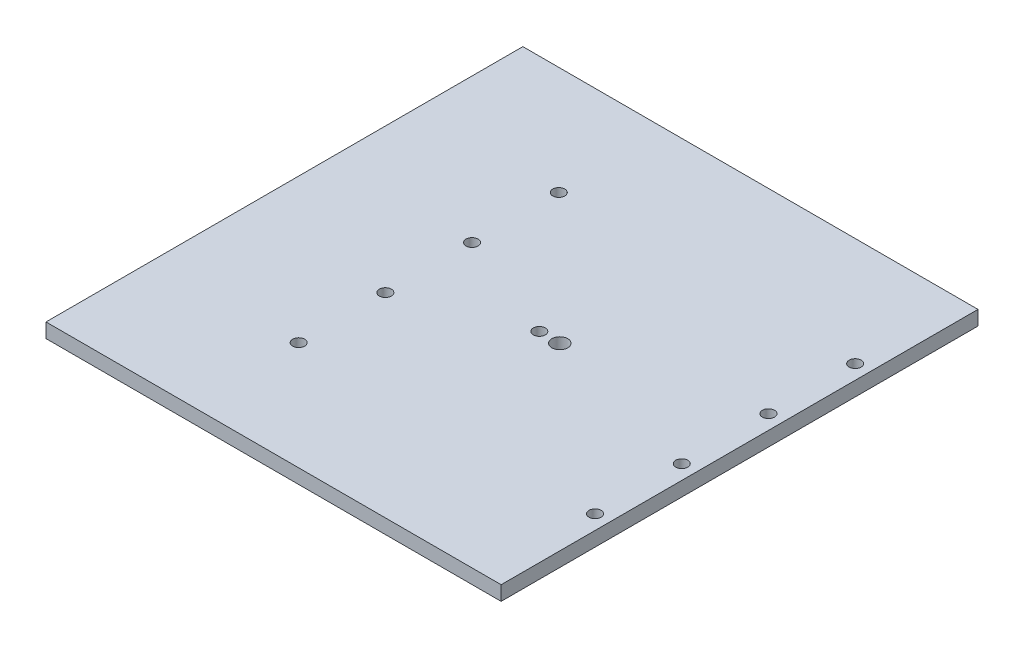
SolidWorks part; units mm, degrees
material "PE High Density"
ref_plane "Front Plane" through (0, 0, 0) normal (0, 0, 1) x (1, 0, 0)
ref_plane "Top Plane" through (0, 0, 0) normal (0, 1, 0) x (1, 0, 0)
ref_plane "Right Plane" through (0, 0, 0) normal (1, 0, 0) x (0, 0, -1)
sketch "Sketch1" plane through (0, 0, 0) normal (0, 1, 0) x (1, 0, 0)
  line L1 (-100, -104.775) -> (100, -104.775)
  line L2 (-100, -104.775) -> (-100, 104.775)
  line L3 (-100, 104.775) -> (100, 104.775)
  line L4 (100, -104.775) -> (100, 104.775)
  line L5 (-100, -104.775) -> (100, 104.775) construction
  line L6 (-100, 104.775) -> (100, -104.775) construction
  point P0 (0, 0)
  dimension "D1" = 200
  dimension "D2" = 209.55
extrude "Boss-Extrude1" add sketch "Sketch1" along normal mid plane 6.35
sketch "Sketch2" plane through (0, 3.175, 0) normal (0, 1, 0) x (1, 0, 0)
  line L0 (-100, -104.775) -> (100, -104.775) construction
  line L1 (100, 104.775) -> (87.3, 104.775) construction
  line L2 (100, 104.775) -> (100, -104.775) construction
  line L3 (100, -104.775) -> (87.3, -104.775) construction
  line L4 (87.3, 104.775) -> (87.3, -104.775) construction
  line L5 (100, 104.775) -> (-100, 104.775) construction
  line L6 (-30.25, 104.775) -> (-42.95, 104.775) construction
  line L7 (-30.25, 104.775) -> (-30.25, -104.775) construction
  line L8 (-30.25, -104.775) -> (-42.95, -104.775) construction
  line L9 (-42.95, 104.775) -> (-42.95, -104.775) construction
  line L10 (93.65, 104.775) -> (93.65, -104.775) construction
  line L11 (-36.6, 104.775) -> (-36.6, -104.775) construction
  point P17 (93.65, 57.15)
  point P18 (-36.6, 57.15)
  point P20 (93.65, 19.05)
  point P21 (-36.6, 19.05)
  point P22 (93.65, -19.05)
  point P23 (-36.6, -19.05)
  point P24 (93.65, -57.15)
  point P25 (-36.6, -57.15)
  dimension "D1" = 12.7
  dimension "D2" = 12.7
  dimension "D3" = 130.25
  dimension "D4" = 47.625
  dimension "D6" = 38.1
  dimension "D5" = 4
hole_wizard "M5 Clearance Hole1" positions "Sketch3" profile "Sketch4" hole size "M5" standard "ANSI Metric" end condition up to next
sketch "Sketch3" plane through (0, 3.175, 0) normal (0, 1, 0) x (1, 0, 0)
  point P0 (-36.6, 57.15)
  point P3 (-36.6, 19.05)
  point P6 (-36.6, -19.05)
  point P9 (-36.6, -57.15)
  point P12 (93.65, -57.15)
  point P15 (93.65, -19.05)
  point P18 (93.65, 19.05)
  point P21 (93.65, 57.15)
sketch "Sketch4" plane through (-36.6, 3.175, -57.15) normal (1, 0, 0) x (0, 0, 1)
  line L0 (0, 0) -> (0, 6.35)
  line L1 (0, 6.35) -> (2.65, 6.35)
  line L2 (2.65, 6.35) -> (2.65, 0)
  line L5 (2.65, 0) -> (0, 0)
  line L11 (0, -6.35) -> (0, 107.95) construction
  dimension "Thru Hole Dia." = 5.3
  dimension "Thru Hole Depth" = 6.35
sketch "Sketch5" plane through (0, 3.175, 0) normal (0, 1, 0) x (1, 0, 0)
  circle A1 centre (21, 0) radius 3.5
  point P0 (12, 0)
  dimension "D3" = 7
  dimension "D1" = 12
  dimension "D2" = 9
extrude "Cut-Extrude1" cut sketch "Sketch5" against normal through all
hole_wizard "M5 Clearance Hole2" positions "Sketch6" profile "Sketch7" hole size "M5" standard "ANSI Metric" end condition through all
sketch "Sketch6" plane through (0, 3.175, 0) normal (0, 1, 0) x (1, 0, 0)
  point P0 (12, 0)
sketch "Sketch7" plane through (12, 3.175, 0) normal (1, 0, 0) x (0, 0, 1)
  line L0 (0, 0) -> (0, 6.35)
  line L1 (0, 6.35) -> (2.65, 6.35)
  line L2 (2.65, 6.35) -> (2.65, 0)
  line L5 (2.65, 0) -> (0, 0)
  line L11 (0, -6.35) -> (0, 107.95) construction
  dimension "Thru Hole Dia." = 5.3
  dimension "Thru Hole Depth" = 6.35
equation "\"D2@Sketch1\"=8.25in"
equation "\"D1@Boss-Extrude1\"=0.25in"
equation "\"D1@Sketch2\"=0.5in"
equation "\"D2@Sketch2\"=0.5in"
equation "\"D4@Sketch2\"=1.5in + 0.75in/2"
